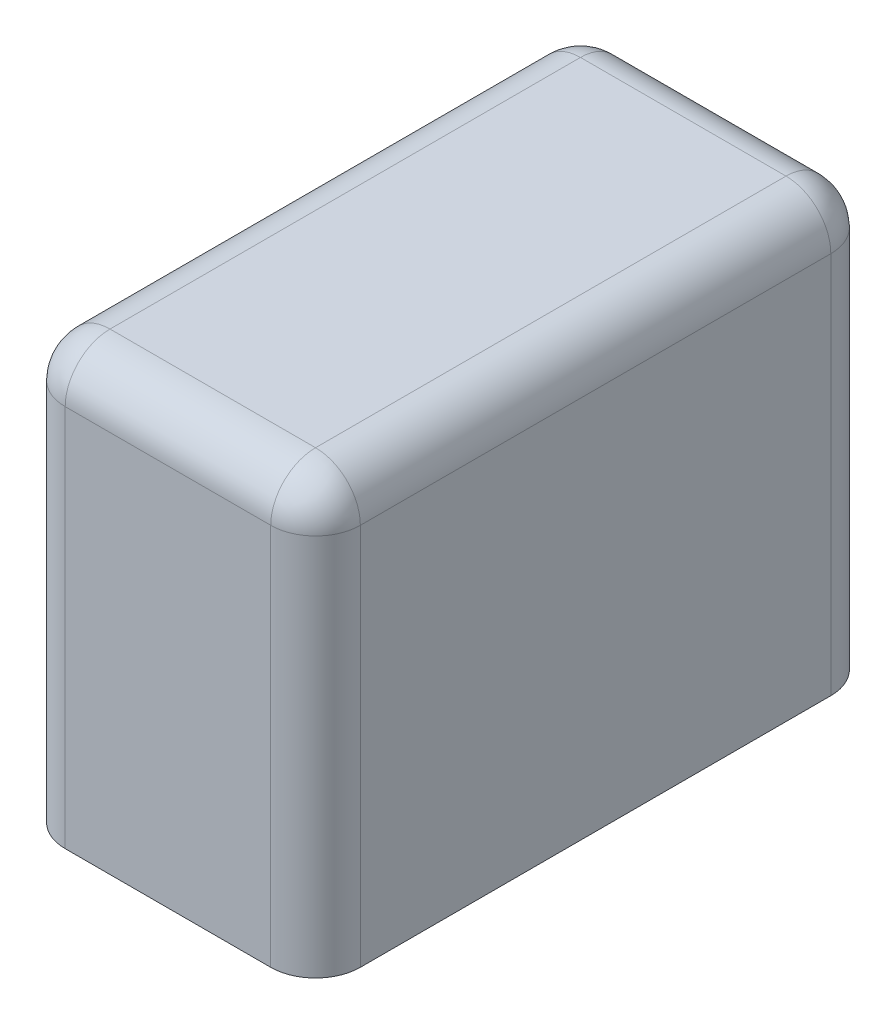
SolidWorks part; units mm, degrees
ref_plane "Front Plane" through (0, 0, 0) normal (0, 0, 1) x (1, 0, 0)
ref_plane "Top Plane" through (0, 0, 0) normal (0, 1, 0) x (1, 0, 0)
ref_plane "Right Plane" through (0, 0, 0) normal (1, 0, 0) x (0, 0, -1)
sketch "Sketch1" plane through (0, 0, 0) normal (0, 1, 0) x (1, 0, 0)
  line L1 (-13.175, 25) -> (13.175, 25)
  line L2 (-13.175, 25) -> (-13.175, -25)
  line L3 (-13.175, -25) -> (13.175, -25)
  line L4 (13.175, 25) -> (13.175, -25)
  line L5 (-13.175, 25) -> (13.175, -25) construction
  line L6 (-13.175, -25) -> (13.175, 25) construction
  line L7 (-10, 21.825) -> (10, 21.825)
  line L8 (-10, 21.825) -> (-10, -21.825)
  line L9 (-10, -21.825) -> (10, -21.825)
  line L10 (10, 21.825) -> (10, -21.825)
  line L11 (-10, 21.825) -> (10, -21.825) construction
  line L12 (-10, -21.825) -> (10, 21.825) construction
  point P0 (0, 0)
  point P6 (0, 0)
  dimension "D1" = 3.175
  dimension "D2" = 3.175
  dimension "D3" = 20
  dimension "D4" = 50
extrude "Boss-Extrude1" add sketch "Sketch1" along normal blind 35
sketch "Sketch2" plane through (0, 35, 0) normal (0, 1, 0) x (1, 0, 0)
  line L1 (-13.175, -25) -> (13.175, -25)
  line L2 (-13.175, -25) -> (-13.175, 25)
  line L3 (-13.175, 25) -> (13.175, 25)
  line L4 (13.175, -25) -> (13.175, 25)
extrude "Boss-Extrude2" add sketch "Sketch2" along normal blind 3.175
sketch "Sketch4" plane through (0, 0, 0) normal (0, -1, 0) x (1, 0, 0)
  line L0 (10, 21.825) -> (10, -21.825) construction
  line L2 (13.175, -25) -> (-13.175, -25) construction
  line L3 (-13.175, 0) -> (13.175, 0) construction
  line L4 (-13.175, -25) -> (-13.175, 25) construction
  line L5 (13.175, 25) -> (13.175, -25) construction
  line L17 (-8.6, -20) -> (-8.6, -21.825)
  line L18 (10, -21.825) -> (-10, -21.825) construction
  line L19 (-1.4, -20) -> (-1.4, -21.825)
  line L20 (-8.6, 21.825) -> (-1.4, 21.825)
  line L21 (-1.4, 20) -> (-1.4, 21.825)
  line L22 (-8.6, -21.825) -> (-1.4, -21.825)
  line L23 (-8.6, 20) -> (-8.6, 21.825)
  arc A4 (-1.4, -20) -> (-8.6, -20) centre (-5, -20) ccw
  arc A5 (-1.4, 20) -> (-8.6, 20) centre (-5, 20) cw
  dimension "D1" = 7.2
  dimension "D2" = 5
  dimension "D3" = 15
extrude "Boss-Extrude3" add sketch "Sketch4" against normal blind 5
fillet "Fillet1" radius 4 8 edges at (-13.175, 38.175, 0) (-13.175, 19.0875, -25) (0, 38.175, -25) (13.175, 19.0875, -25) (13.175, 38.175, 0) (0, 38.175, 25) (13.175, 19.0875, 25) (-13.175, 19.0875, 25)
sketch "Sketch6" plane through (-13.175, 0, 0) normal (-1, 0, 0) x (0, 0, 1)
  line L0 (0, 34.175) -> (0, 0) construction
  line L5 (21, 34.175) -> (-21, 34.175) construction
  line L8 (-21, 0) -> (21, 0) construction
  line L9 (-10, 18.175) -> (0, 18.175) construction
  line L10 (-5, 23.175) -> (5, 23.175)
  line L11 (-5, 23.175) -> (-5, 18.175)
  line L12 (-5, 18.175) -> (5, 18.175)
  line L13 (5, 23.175) -> (5, 18.175)
  line L14 (-5, 23.175) -> (5, 18.175) construction
  line L15 (-5, 18.175) -> (5, 23.175) construction
  point P6 (0, 20.675)
  dimension "D1" = 10
  dimension "D2" = 5
  dimension "D3" = 0
extrude "Cut-Extrude3" cut sketch "Sketch6" against normal blind 3.175
sketch "Sketch8" plane through (0, 0, 0) normal (0, -1, 0) x (1, 0, 0)
  line L0 (-13.175, 0) -> (13.175, 0) construction
  line L1 (-13.175, -21) -> (-13.175, 21) construction
  line L2 (13.175, 21) -> (13.175, -21) construction
  circle A0 centre (-5, -20) radius 3.05
  circle A1 centre (-5, 20) radius 3.05
  dimension "D1" = 6.1
extrude "Cut-Extrude5" cut sketch "Sketch8" against normal blind 2.7
sketch "Sketch9" plane through (13.175, 0, 0) normal (1, 0, 0) x (0, 0, -1)
  line L0 (0, 34.175) -> (0, 0) construction
  line L2 (-21, 0) -> (21, 0) construction
  line L3 (16.5, 13.875) -> (16.5, 9.875)
  line L4 (-12.25, 13.875) -> (-6.25, 13.875)
  line L5 (-12.25, 13.875) -> (-12.25, 9.875)
  line L6 (-12.25, 9.875) -> (-6.25, 9.875)
  line L7 (-6.25, 13.875) -> (-6.25, 9.875)
  line L8 (22.5, 9.875) -> (16.5, 9.875)
  line L9 (22.5, 13.875) -> (22.5, 9.875)
  line L10 (22.5, 13.875) -> (16.5, 13.875)
  line L11 (21, 34.175) -> (-21, 34.175) construction
  dimension "D1" = 6
  dimension "D2" = 4
  dimension "D4" = 9.875
  dimension "D3" = 22.75
  dimension "D5" = 6.25
  dimension "D7" = 0
  dimension "D8" = 4
  dimension "D6" = 6
extrude "Boss-Extrude4" add sketch "Sketch9" against normal blind 12.5 from surface starting at face at (10, 17.5, 0)
sketch "Sketch10" plane through (0, 9.875, 0) normal (0, -1, 0) x (1, 0, 0)
  line L0 (-16.5229, 0) -> (15.3543, 0) construction
  line L1 (10, 21.825) -> (10, -21.825) construction
  circle A0 centre (3.75, 8.575) radius 1
  circle A1 centre (3.75, -18.825) radius 1
  dimension "D3" = 2
  dimension "D1" = 27.4
  dimension "D2" = 6.25
  dimension "D4" = 8.575
extrude "Cut-Extrude6" cut sketch "Sketch10" against normal blind 15.675
equation "\"D8@Sketch9\"=\"D2@Sketch9\""
equation "\"D6@Sketch9\"=\"D1@Sketch9\""
